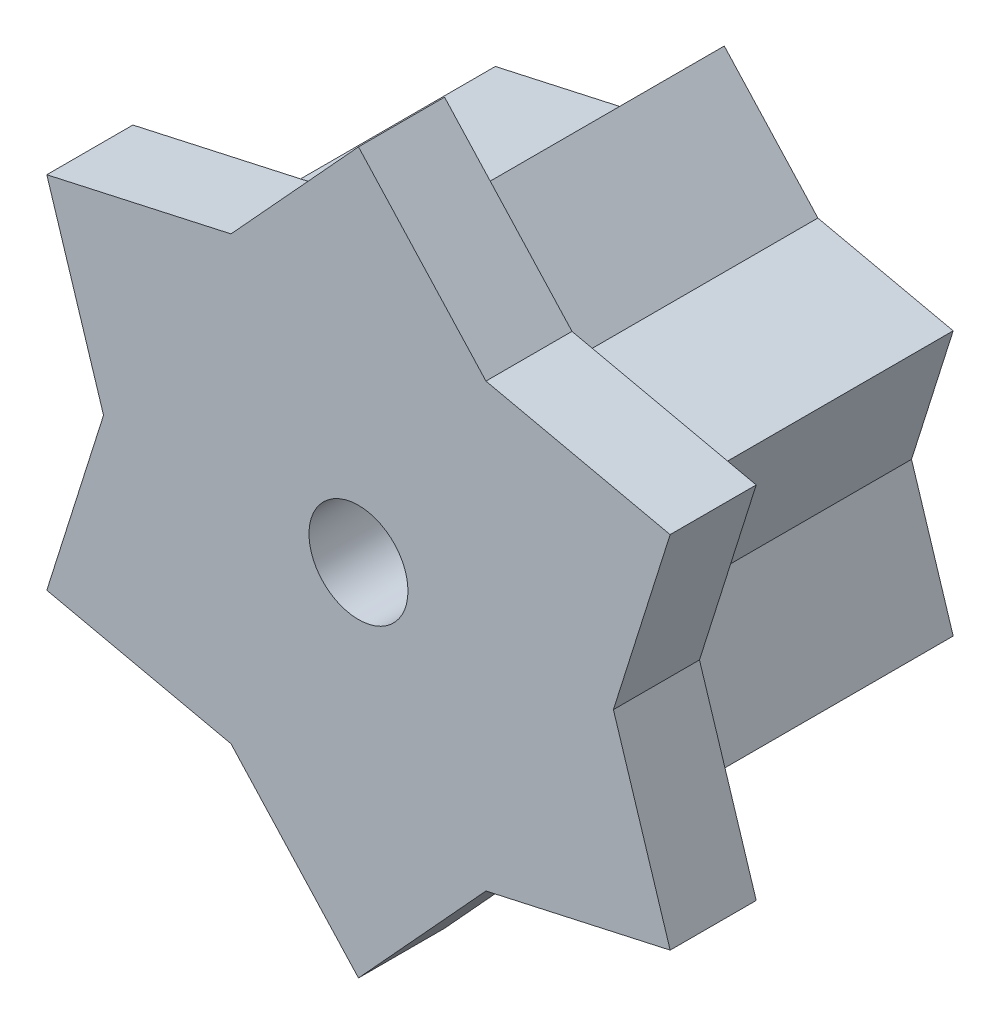
SolidWorks part; units mm, degrees
ref_plane "Front Plane" through (0, 0, 0) normal (0, 0, 1) x (1, 0, 0)
ref_plane "Top Plane" through (0, 0, 0) normal (0, 1, 0) x (1, 0, 0)
ref_plane "Right Plane" through (0, 0, 0) normal (1, 0, 0) x (0, 0, -1)
sketch "Sketch1" plane through (0, 0, 0) normal (0, 0, 1) x (1, 0, 0)
  line L0 (0, 6.1428) -> (0, -5.749) construction
  line L1 (-3.0597, 2.8037) -> (0, 6.1428)
  line L2 (0, 6.1428) -> (3.0597, 2.8037)
  line L3 (0.8982, 4.0516) -> (5.3198, 3.0714)
  line L4 (5.3198, 3.0714) -> (3.9579, -1.2479)
  line L5 (3.9579, 1.2479) -> (5.3198, -3.0714)
  line L6 (5.3198, -3.0714) -> (0.8982, -4.0516)
  line L7 (3.0597, -2.8037) -> (0, -6.1428)
  line L8 (0, -6.1428) -> (-3.0597, -2.8037)
  line L9 (-0.8982, -4.0516) -> (-5.3198, -3.0714)
  line L10 (-5.3198, -3.0714) -> (-3.9579, 1.2479)
  line L11 (-3.9579, -1.2479) -> (-5.3198, 3.0714)
  line L12 (-5.3198, 3.0714) -> (-0.8982, 4.0516)
  circle A0 centre (0, 0) radius 1.15
  circle A1 centre (0, 0) radius 4.15
  point P26 (0, 0)
  dimension "D1" = 2.3
  dimension "D3" = 85
  dimension "D4" = 42.5
  dimension "D2" = 3
  dimension "D5" = 6
extrude "Boss-Extrude1" add sketch "Sketch1" against normal blind 6.5 contours A1 A0 | A1 L1 L12 L11 L10 | L2 L0 A1 L3 | L0 L1 L12 A1 | A1 L12 L1 | A1 L2 L3 | A1 L5 L4 L3 L2 | L0 A1 A0 | A1 L11 L10 L9 L8 | A1 L10 L11 | A1 L8 L9 | A1 L9 L8 L7 L6 | A1 L6 L7 | A1 L7 L6 L5 L4 | A1 L4 L5 | A0 L0 | L0 A0 region at (0.718, 4.7126, 0) region at (-0.718, 4.7126, 0) region at (1.8672, 0, 0) region at (-1.8672, 0, 0) region at (-2.0957, 3.6299, 0) region at (-4.0813, 2.3563, 0) region at (4.0813, 2.3563, 0) region at (2.0957, 3.6299, 0) region at (0.4881, 0, 0) region at (-0.4881, 0, 0) region at (-4.1915, 0, 0) region at (-4.0813, -2.3563, 0) region at (4.1915, 0, 0) region at (4.0813, -2.3563, 0) region at (0.4572, -4.1746, 0) region at (-2.0957, -3.6299, 0) region at (2.0957, -3.6299, 0)
sketch "Sketch2" plane through (0, 0, 0) normal (0, 0, 1) x (1, 0, 0)
  line L0 (2.9621, 5.1305) -> (0, 8.3631)
  line L1 (0, 8.3631) -> (-2.9621, 5.1305)
  line L2 (-2.9621, 5.1305) -> (-7.2426, 4.1815)
  line L3 (-7.2426, 4.1815) -> (-5.9242, 0)
  line L4 (-5.9242, 0) -> (-7.2426, -4.1815)
  line L5 (-7.2426, -4.1815) -> (-2.9621, -5.1305)
  line L6 (-2.9621, -5.1305) -> (0, -8.3631)
  line L7 (0, -8.3631) -> (2.9621, -5.1305)
  line L8 (2.9621, -5.1305) -> (7.2426, -4.1815)
  line L9 (7.2426, -4.1815) -> (5.9242, 0)
  line L10 (5.9242, 0) -> (7.2426, 4.1815)
  line L11 (7.2426, 4.1815) -> (2.9621, 5.1305)
  line L12 (5.3198, -3.0714) -> (4.3514, 0)
  line L13 (4.3514, 0) -> (5.3198, 3.0714)
  line L14 (5.3198, 3.0714) -> (2.1757, 3.7684)
  line L15 (2.1757, 3.7684) -> (0, 6.1428)
  line L16 (0, 6.1428) -> (-2.1757, 3.7684)
  line L17 (-2.1757, 3.7684) -> (-5.3198, 3.0714)
  line L18 (-5.3198, 3.0714) -> (-4.3514, 0)
  line L19 (-4.3514, 0) -> (-5.3198, -3.0714)
  line L20 (-5.3198, -3.0714) -> (-2.1757, -3.7684)
  line L21 (-2.1757, -3.7684) -> (0, -6.1428)
  line L22 (0, -6.1428) -> (2.1757, -3.7684)
  line L23 (2.1757, -3.7684) -> (5.3198, -3.0714)
  line L24 (5.3198, -3.0714) -> (4.3514, 0)
  line L25 (4.3514, 0) -> (5.3198, 3.0714)
  line L26 (5.3198, 3.0714) -> (2.1757, 3.7684)
  line L27 (2.1757, 3.7684) -> (0, 6.1428)
  line L28 (0, 6.1428) -> (-2.1757, 3.7684)
  line L29 (-2.1757, 3.7684) -> (-5.3198, 3.0714)
  line L30 (-5.3198, 3.0714) -> (-4.3514, 0)
  line L31 (-4.3514, 0) -> (-5.3198, -3.0714)
  line L32 (-5.3198, -3.0714) -> (-2.1757, -3.7684)
  line L33 (-2.1757, -3.7684) -> (0, -6.1428)
  line L34 (0, -6.1428) -> (2.1757, -3.7684)
  line L35 (2.1757, -3.7684) -> (5.3198, -3.0714)
  line M25 (5.3198, -3.0714) -> (4.3514, 0)
  line M26 (4.3514, 0) -> (5.3198, 3.0714)
  line M27 (5.3198, 3.0714) -> (2.1757, 3.7684)
  line M28 (2.1757, 3.7684) -> (0, 6.1428)
  line M29 (0, 6.1428) -> (-2.1757, 3.7684)
  line M30 (-2.1757, 3.7684) -> (-5.3198, 3.0714)
  line M31 (-5.3198, 3.0714) -> (-4.3514, 0)
  line M32 (-4.3514, 0) -> (-5.3198, -3.0714)
  line M33 (-5.3198, -3.0714) -> (-2.1757, -3.7684)
  line M34 (-2.1757, -3.7684) -> (0, -6.1428)
  line M35 (0, -6.1428) -> (2.1757, -3.7684)
  line M36 (2.1757, -3.7684) -> (5.3198, -3.0714)
  dimension "D1" = 0
  dimension "D2" = 1.5
extrude "Boss-Extrude2" add sketch "Sketch2" along normal blind 2 contours M36 M25 M26 M27 M28 M29 M30 M31 M32 M33 M34 M35 | L10 L11 L0 L1 L2 L3 L4 L5 L6 L7 L8 L9 M25 M36 M35 M34 M33 M32 M31 M30 M29 M28 M27 M26 region at (5.0545, 4.44, 0) region at (0, 0, 0)
extrude "Cut-Extrude1" cut sketch "Sketch1<4>" against normal through all both and the other way through all contours A0 L0 | L0 A0 region at (0.4881, 0, 0) region at (-0.4881, 0, 0)
sketch "Sketch1<4>" plane through (0, 0, 0) normal (0, 0, 1) x (1, 0, 0) same geometry as "Sketch1"
chamfer "Chamfer1" distance 0.4 angle 45 12 edges at (3.7477, -3.4199, 0) (1.0878, -4.9556, 0) (-1.0878, -4.9556, 0) (-3.7477, -3.4199, 0) (-4.8356, -1.5357, 0) (-4.8356, 1.5357, 0) (-3.7477, 3.4199, 0) (4.8356, -1.5357, 0) (4.8356, 1.5357, 0) (3.7477, 3.4199, 0) (1.0878, 4.9556, 0) (-1.0878, 4.9556, 0)
